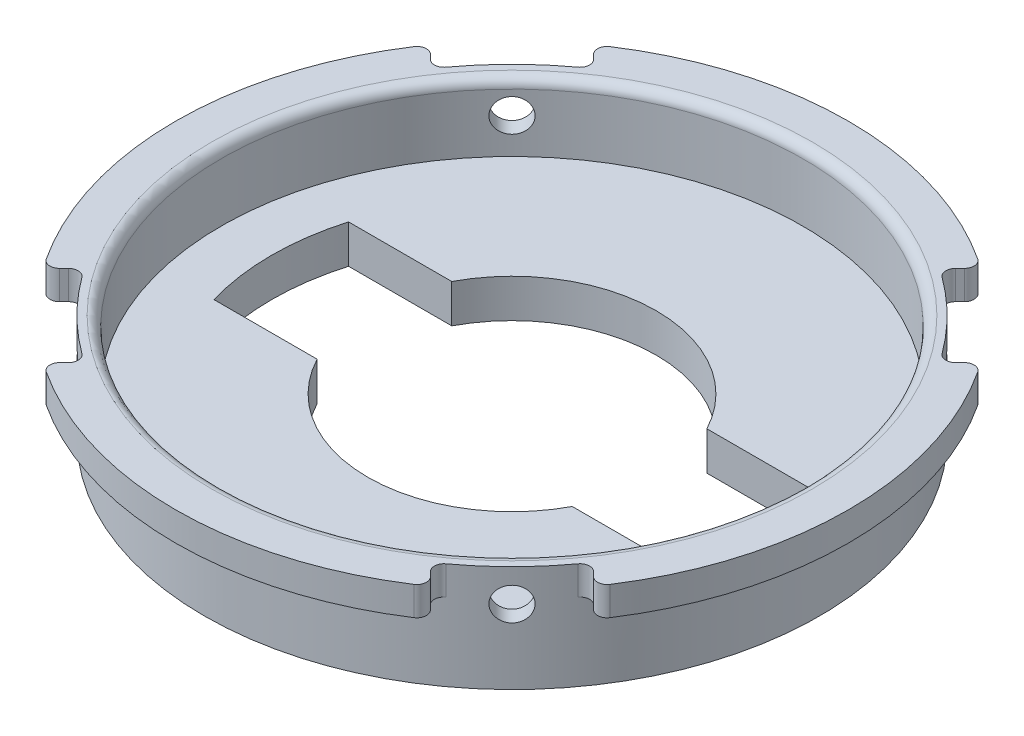
SolidWorks part; units mm, degrees
material "AISI 304"
ref_plane "前视基准面" through (0, 0, 0) normal (0, 0, 1) x (1, 0, 0)
ref_plane "上视基准面" through (0, 0, 0) normal (0, 1, 0) x (1, 0, 0)
ref_plane "右视基准面" through (0, 0, 0) normal (1, 0, 0) x (0, 0, -1)
sketch "草图1" plane through (0, 0, 0) normal (0, 1, 0) x (1, 0, 0)
  circle A0 centre (0, 0) radius 32
  dimension "D1" = 64
extrude "凸台-拉伸1" add sketch "草图1" along normal blind 2
sketch "草图2" plane through (0, 2, 0) normal (0, 1, 0) x (1, 0, 0)
  circle A0 centre (0, 0) radius 15
  dimension "D1" = 30
extrude "切除-拉伸1" cut sketch "草图2" against normal blind 2
sketch "草图3" plane through (0, 2, 0) normal (0, 1, 0) x (1, 0, 0)
  line L0 (-32, 0) -> (32, 0) construction
  line L1 (0, 32) -> (0, -32) construction
  line L2 (-24, 7) -> (24, 7)
  line L3 (-24, -7) -> (24, -7)
  arc A0 (-24, 7) -> (-24, -7) centre (0, 0) ccw
  circle A1 centre (0, 0) radius 32 construction
  arc A2 (0, 25) -> (-24, 7) centre (0, 0) ccw construction
  arc A3 (24, 7) -> (0, 25) centre (0, 0) ccw construction
  arc A4 (24, -7) -> (24, 7) centre (0, 0) ccw
  arc A5 (-24, -7) -> (0, -25) centre (0, 0) ccw construction
  arc A6 (0, -25) -> (24, -7) centre (0, 0) ccw construction
  point P13 (0, 7)
  dimension "D1" = 50
  dimension "D2" = 14
extrude "切除-拉伸2" cut sketch "草图3" against normal blind 2
sketch "草图4" plane through (0, 2, 0) normal (0, 1, 0) x (1, 0, 0)
  circle A0 centre (0, 0) radius 32
  circle A1 centre (0, 0) radius 30.25
  dimension "D1" = 64
  dimension "D2" = 60.5
extrude "凸台-拉伸2" add sketch "草图4" along normal blind 7.07
sketch "草图5" plane through (0, 0, 0) normal (0, 1, 0) x (1, 0, 0)
  line L0 (0, 35.9944) -> (0, -35.9944)
  line L1 (-48.0979, 0) -> (48.0979, 0)
  line L2 (-33.5104, 33.5104) -> (33.5104, -33.5104)
  line L3 (-30.6652, -30.6652) -> (30.6652, 30.6652)
  point P4 (0, 0)
  point P8 (0, 0)
  point P11 (0, 0)
  point P14 (0, 0)
  dimension "D1" = 45
  dimension "D2" = 45
ref_plane "基准面4" through (0, 0, 0) normal (0.7071, 0, 0.7071) x (0.7071, 0, -0.7071)
ref_plane "基准面5" through (0, 0, 0) normal (-0.7071, 0, 0.7071) x (0.7071, 0, 0.7071)
sketch "草图6" plane through (0, 0, 0) normal (0.7071, 0, 0.7071) x (0.7071, 0, -0.7071)
  line L0 (0, 52.13) -> (0, -52.13) construction
  line L1 (-32, 0) -> (32, 0) construction
  circle A0 centre (0, 5.7) radius 1.7
  dimension "D1" = 3.4
  dimension "D2" = 5.7
extrude "切除-拉伸3" cut sketch "草图6" against normal blind 37.05 and the other way blind 36.05
sketch "草图7" plane through (0, 0, 0) normal (-0.7071, 0, 0.7071) x (0.7071, 0, 0.7071)
  line L0 (0, -47.7039) -> (0, 47.7039) construction
  line L1 (-32, 0) -> (32, 0) construction
  circle A0 centre (0, 5.7) radius 1.7
  dimension "D1" = 3.4
  dimension "D2" = 5.7
extrude "切除-拉伸4" cut sketch "草图7" against normal blind 37.05 and the other way blind 37.05
sketch "草图8" plane through (0, 9.07, 0) normal (0, 1, 0) x (1, 0, 0)
  circle A0 centre (0, 0) radius 32
  circle A1 centre (0, 0) radius 35
  dimension "D1" = 64
  dimension "D2" = 70
extrude "凸台-拉伸3" add sketch "草图8" against normal blind 3
sketch "草图9" plane through (0, 9.07, 0) normal (0, 1, 0) x (1, 0, 0)
  line L0 (0, 35) -> (0, -35) construction
  line L1 (-35, 0) -> (35, 0) construction
  line L2 (0, 0) -> (35, -35) construction
  line L3 (22.6274, -22.6274) -> (31.8606, -31.8606) construction
  line L4 (27.618, -36.1032) -> (36.1032, -27.618)
  line L5 (36.1032, -27.618) -> (26.4688, -17.9835)
  line L6 (27.618, -36.1032) -> (17.9835, -26.4688)
  line L7 (-27.618, -36.1032) -> (-17.9835, -26.4688)
  line L8 (-36.1032, -27.618) -> (-26.4688, -17.9835)
  line L9 (-36.1032, -27.618) -> (-27.618, -36.1032)
  line L10 (-36.1032, 27.618) -> (-26.4688, 17.9835)
  line L11 (-27.618, 36.1032) -> (-17.9835, 26.4688)
  line L12 (-27.618, 36.1032) -> (-36.1032, 27.618)
  line L13 (27.618, 36.1032) -> (17.9835, 26.4688)
  line L14 (36.1032, 27.618) -> (26.4688, 17.9835)
  line L15 (36.1032, 27.618) -> (27.618, 36.1032)
  arc A0 (17.9835, -26.4688) -> (26.4688, -17.9835) centre (0, 0) ccw
  circle A1 centre (0, 0) radius 35 construction
  arc A2 (0, 32) -> (-32, 0) centre (0, 0) ccw construction
  arc A3 (32, 0) -> (0, 32) centre (0, 0) ccw construction
  arc A4 (-32, 0) -> (0, -32) centre (0, 0) ccw construction
  arc A5 (0, -32) -> (17.9835, -26.4688) centre (0, 0) ccw construction
  arc A6 (26.4688, -17.9835) -> (32, 0) centre (0, 0) ccw construction
  arc A7 (-26.4688, -17.9835) -> (-17.9835, -26.4688) centre (0, 0) ccw
  arc A8 (-17.9835, 26.4688) -> (-26.4688, 17.9835) centre (0, 0) ccw
  arc A9 (26.4688, 17.9835) -> (17.9835, 26.4688) centre (0, 0) ccw
  point P10 (22.6274, -22.6274)
  dimension "D1" = 64
  dimension "D3" = 12
  dimension "D2" = 4
extrude "切除-拉伸5" cut sketch "草图9" against normal blind 4
fillet "圆角1" radius 1 16 edges at (-20.1397, 7.57, 28.625) (-28.625, 7.57, 20.1397) (-26.4688, 7.57, 17.9835) (-17.9835, 7.57, 26.4688) (26.4688, 7.57, 17.9835) (28.625, 7.57, 20.1397) (20.1397, 7.57, 28.625) (17.9835, 7.57, 26.4688) (28.625, 7.57, -20.1397) (26.4688, 7.57, -17.9835) (20.1397, 7.57, -28.625) (17.9835, 7.57, -26.4688) (-20.1397, 7.57, -28.625) (-17.9835, 7.57, -26.4688) (-28.625, 7.57, -20.1397) (-26.4688, 7.57, -17.9835)
fillet "圆角2" radius 1 1 edges at (0, 9.07, 30.25)
sketch "草图10" plane through (0, 0, 0) normal (0, -1, 0) x (1, 0, 0)
  line L0 (-24, 7) -> (-13.2665, 7)
  line L1 (-24, -7) -> (-13.2665, -7)
  line L2 (13.2665, 7) -> (24, 7)
  line L3 (-13.2665, 7) -> (13.2665, 7) construction
  line L4 (13.2665, -7) -> (24, -7)
  line L5 (-13.2665, -7) -> (13.2665, -7) construction
  circle A0 centre (0, 0) radius 32
  arc A1 (-13.2665, -7) -> (13.2665, -7) centre (0, 0) ccw
  arc A2 (-24, 7) -> (-24, -7) centre (0, 0) ccw
  arc A3 (-13.2665, 7) -> (-13.2665, -7) centre (0, 0) ccw construction
  arc A4 (13.2665, 7) -> (-13.2665, 7) centre (0, 0) ccw
  arc A5 (13.2665, -7) -> (13.2665, 7) centre (0, 0) ccw construction
  arc A6 (24, 7) -> (-24, 7) centre (0, 0) ccw construction
  arc A7 (24, -7) -> (24, 7) centre (0, 0) ccw
  arc A8 (-24, -7) -> (24, -7) centre (0, 0) ccw construction
extrude "凸台-拉伸4" add sketch "草图10" along normal blind 2
